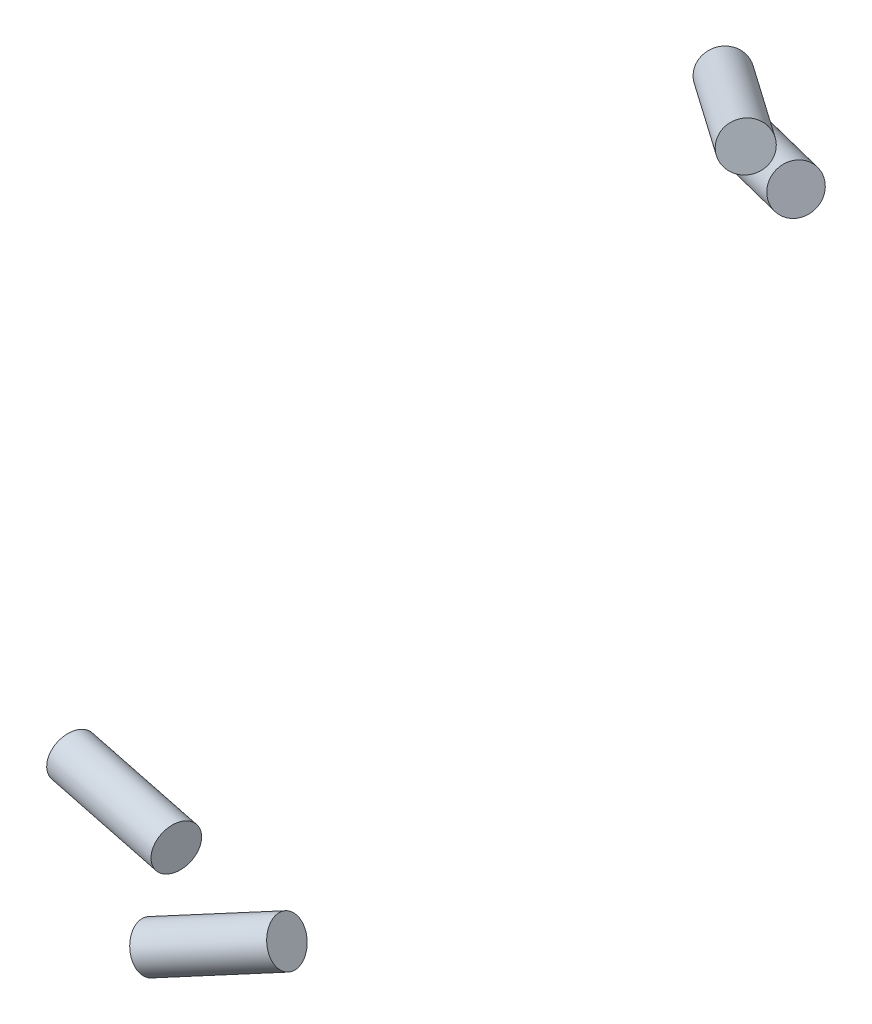
SolidWorks part; units mm, degrees
ref_plane "Plano frontal" through (0, 0, 0) normal (0, 0, 1) x (1, 0, 0)
ref_plane "Plano superior" through (0, 0, 0) normal (0, 1, 0) x (1, 0, 0)
ref_plane "Plano direito" through (0, 0, 0) normal (1, 0, 0) x (0, 0, -1)
sketch3d "SUSP_RR_rocker_bracket_a_eixo"
  line L0 (217.9678, 1156.3192, -69.0971) -> (259.065, 1155.1096, -61.5712)
sweep "SUSP_RR_rocker_bracket_a" add path "SUSP_RR_rocker_bracket_a_eixo" circular profile diameter 14 parameters "D3"=14
sketch3d "SUSP_RR_rocker_bracket_b_eixo"
  line L0 (231.565, 1104.0299, -80.5983) -> (268.815, 1120.8704, -87.4288)
sweep "SUSP_RR_rocker_bracket_b" add path "SUSP_RR_rocker_bracket_b_eixo" circular profile diameter 14 parameters "D3"=14
sketch3d "SUSP_RR_coilover_bracket_a_eixo"
  line L0 (238.2798, 1261.6845, -258.541) -> (272.1505, 1271.9554, -231.7798)
sweep "SUSP_RR_coilover_bracket_a" add path "SUSP_RR_coilover_bracket_a_eixo" circular profile diameter 14 parameters "D3"=14
sketch3d "SUSP_RR_coilover_bracket_b_eixo"
  line L0 (243.9847, 1245.821, -259.6731) -> (276.5823, 1256.3922, -243.5332)
sweep "SUSP_RR_coilover_bracket_b" add path "SUSP_RR_coilover_bracket_b_eixo" circular profile diameter 14 parameters "D3"=14
sketch3d "REF_SKETCH"
  line L0 (251, 1212.7911, -263.659) -> (259, 1217.5911, -260.059)
  line L1 (257.4, 1212.1911, -265.059) -> (252.6, 1218.1911, -258.659)
  line L2 (255, 1215.1911, -261.859) -> (210, 1340.3211, -252.929)
  line L3 (211, 1149.2011, -55.449) -> (219, 1154.0011, -51.849)
  line L4 (217.4, 1148.6011, -56.849) -> (212.6, 1154.6011, -50.449)
  line L5 (215, 1151.6011, -53.649) -> (175, 1320.3211, -53.599)
  line L6 (171, 1317.2, -95.8) -> (179, 1322, -92.2)
  line L7 (177.4, 1316.6, -97.2) -> (172.6, 1322.6, -90.8)
  line L8 (259.94, 1135.59, -76.3) -> (267.94, 1140.39, -72.7)
  line L9 (266.34, 1134.99, -77.7) -> (261.54, 1140.99, -71.3)
  line L10 (270.5877, 1114.6451, -92.1302) -> (257.2923, 1161.3349, -56.8698)
  line L11 (270.3664, 1261.7738, -239.4565) -> (278.3664, 1266.5738, -235.8565)
  line L12 (276.7664, 1261.1738, -240.8565) -> (271.9664, 1267.1738, -234.4565)
ref_point "P_UCA_IN_FRONT"
ref_axis "A_UCA_PIVOT" through (255, 1215.1911, -261.859) along (-0.3376, 0.9389, 0.067)
ref_point "P_LCA_IN_FRONT"
ref_axis "A_LCA_PIVOT" through (215, 1151.6011, -53.649) along (-0.2307, 0.973, 0.0003)
ref_point "P_TIE_ROD_IN"
ref_point "P_ROCKER_PIVOT"
ref_axis "A_ROCKER" through (270.5877, 1114.6451, -92.1302) along (-0.2216, 0.7782, 0.5877)
ref_point "P_DAMPER_CHASSIS"
